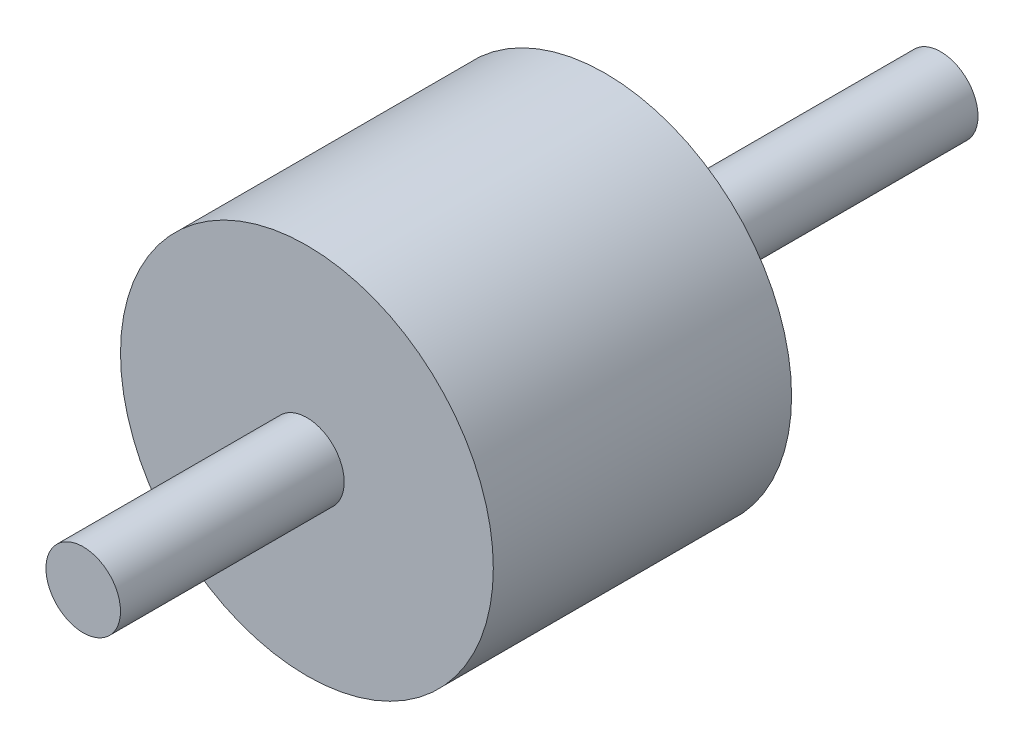
SolidWorks part; units mm, degrees
material "Copper"
ref_plane "Front Plane" through (0, 0, 0) normal (0, 0, 1) x (1, 0, 0)
ref_plane "Top Plane" through (0, 0, 0) normal (0, 1, 0) x (1, 0, 0)
ref_plane "Right Plane" through (0, 0, 0) normal (1, 0, 0) x (0, 0, -1)
sketch "Sketch1" plane through (0, 0, 0) normal (0, 0, 1) x (1, 0, 0)
  circle A0 centre (0, 0) radius 7.5
  circle A1 centre (0, 0) radius 5
  circle A3 centre (0, 0) radius 25
  dimension "D1" = 10
  dimension "D2" = 15
  dimension "D3" = 50
extrude "Boss-Extrude1" add sketch "Sketch1" along normal blind 40 contours A3
extrude "Boss-Extrude2" add sketch "Sketch1<3>" against normal blind 10 contours A0
sketch "Sketch1<3>" plane through (0, 0, 0) normal (0, 0, 1) x (1, 0, 0) same geometry as "Sketch1"
extrude "Boss-Extrude3" add sketch "Sketch1<4>" along normal blind 30 from surface contours A1 starting at face at (25, 0, 40)
sketch "Sketch1<4>" plane through (0, 0, 0) normal (0, 0, 1) x (1, 0, 0) same geometry as "Sketch1"
extrude "Boss-Extrude4" add sketch "Sketch1<5>" against normal blind 115 from surface contours A1 region at (0, 0, 0) starting at face at (5, 0, 70)
sketch "Sketch1<5>" plane through (0, 0, 0) normal (0, 0, 1) x (1, 0, 0) same geometry as "Sketch1"
